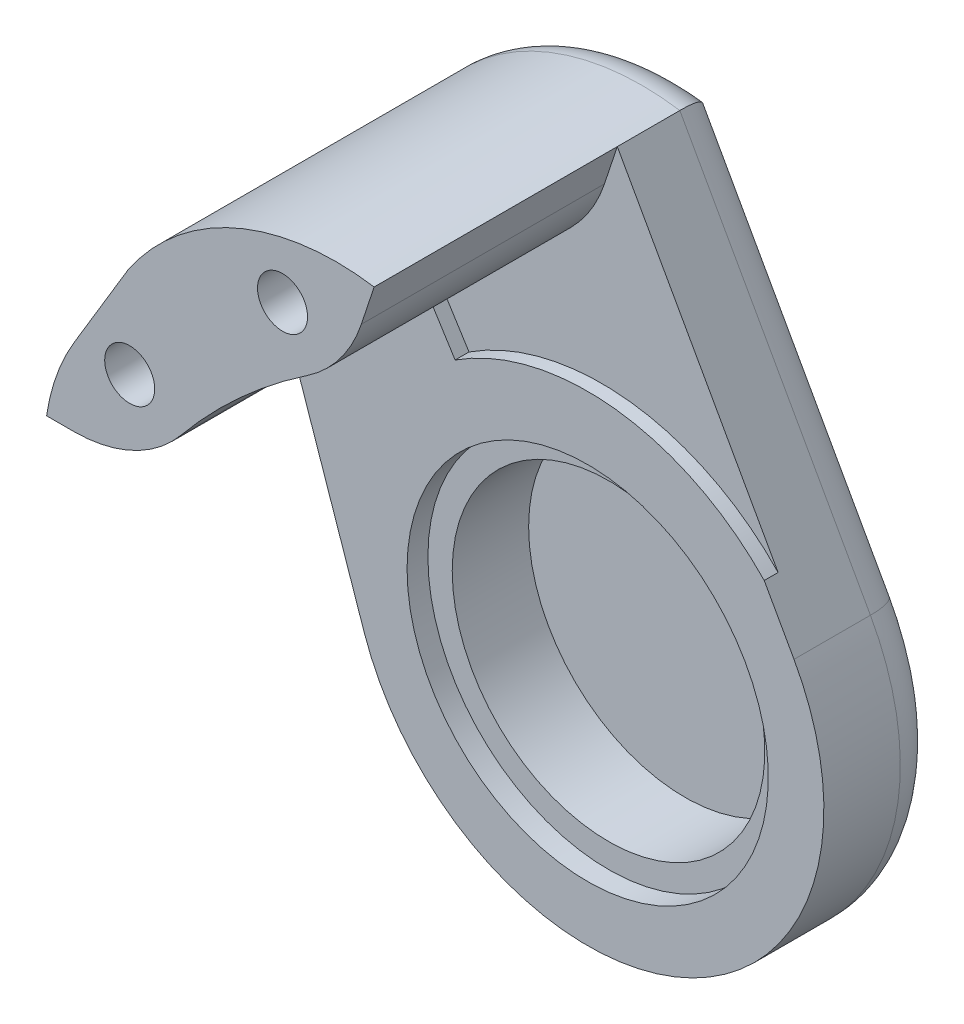
SolidWorks part; units mm, degrees
material "ABS"
ref_plane "Front Plane" through (0, 0, 0) normal (0, 0, 1) x (1, 0, 0)
ref_plane "Top Plane" through (0, 0, 0) normal (0, 1, 0) x (1, 0, 0)
ref_plane "Right Plane" through (0, 0, 0) normal (1, 0, 0) x (0, 0, -1)
sketch "Sketch1" plane through (0, 0, 0) normal (0, 0, 1) x (1, 0, 0)
  line L0 (-21.5118, -23.5649) -> (-14.5118, -23.5649)
  line L1 (0, -9.9671) -> (2.0631, -3.7458)
  line L3 (-15.6677, -11.5659) -> (-19.5301, -18.0027)
  arc A1 (-19.5301, -18.0027) -> (-21.5118, -23.5649) centre (-6.6677, -25.7195) ccw
  arc A2 (-15.6677, -11.5659) -> (2.0631, -3.7458) centre (-0.6677, -21.5651) cw
  arc A3 (-14.5118, -23.5649) -> (0, -9.9671) centre (21.0043, -46.9259) cw
  circle A4 centre (-4.5301, -8.0036) radius 1.8
  circle A5 centre (-15.5301, -18.0027) radius 1.8
  dimension "D1" = 7
  dimension "D8" = 3.6
  dimension "D2" = 2.0631
  dimension "D3" = 3.7458
  dimension "D4" = 16.9817
  dimension "D5" = 15.5614
  dimension "D6" = 5.9817
  dimension "D7" = 5.5622
extrude "Boss-Extrude1" add sketch "Sketch1" along normal blind 21
sketch "Sketch2" plane through (0, 0, 21) normal (0, 0, 1) x (1, 0, 0)
  line L0 (-15.6677, -11.5659) -> (-19.5301, -18.0027) construction
  line L1 (-15.6677, -11.5659) -> (-19.5301, -18.0027)
  line L2 (2.0631, -3.7458) -> (15.7796, -28.3476)
  line L3 (-21.5118, -23.5649) -> (-15.1513, -42.1348)
  arc A0 (-19.5301, -18.0027) -> (-21.5118, -23.5649) centre (-6.6677, -25.7195) ccw construction
  arc A1 (2.0631, -3.7458) -> (-15.6677, -11.5659) centre (-0.6677, -21.5651) ccw construction
  arc A2 (-19.5301, -18.0027) -> (-21.5118, -23.5649) centre (-6.6677, -25.7195) ccw
  arc A3 (2.0631, -3.7458) -> (-15.6677, -11.5659) centre (-0.6677, -21.5651) ccw
  arc A4 (15.7796, -28.3476) -> (-15.1513, -42.1348) centre (0.9315, -36.6261) cw
  circle A5 centre (-15.5301, -18.0027) radius 1.8 construction
  circle A6 centre (-4.5301, -8.0036) radius 1.8 construction
  circle A7 centre (-15.5301, -18.0027) radius 1.8
  circle A8 centre (-4.5301, -8.0036) radius 1.8
  dimension "D1" = 17
  dimension "D2" = 22.4433
  dimension "D3" = 13.0611
extrude "Boss-Extrude2" add sketch "Sketch2" along normal blind 4 and the other way blind 4.5
sketch "Sketch3" plane through (0, 0, 16.5) normal (0, 0, -1) x (-1, 0, 0)
  circle A0 centre (-0.9315, -36.6261) radius 11.25
  dimension "D1" = 22.5
  dimension "D2" = 32.8803
  dimension "D3" = 22.4433
extrude "Cut-Extrude1" cut sketch "Sketch3" against normal blind 7
sketch "Sketch4" plane through (0, 0, 16.5) normal (0, 0, -1) x (-1, 0, 0)
  circle A0 centre (-0.9315, -36.6261) radius 13
  dimension "D1" = 26
extrude "Cut-Extrude2" cut sketch "Sketch4" against normal blind 1.5
sketch "Sketch5" plane through (0, 0, 25) normal (0, 0, 1) x (1, 0, 0)
  circle A0 centre (-4.5301, -8.0036) radius 3
  circle A1 centre (-15.5301, -18.0027) radius 3
  dimension "D1" = 6
extrude "Cut-Extrude3" cut sketch "Sketch5" against normal blind 12
fillet "Fillet1" radius 3 6 edges at (-20.7974, -20.6853, 25) (8.9213, -16.0467, 25) (7.8526, -52.1534, 25) (-17.5989, -14.7843, 25) (-7.9425, -5.0708, 25) (-18.3315, -32.8499, 25)
sketch "Sketch6" plane through (0, 0, 16.5) normal (0, 0, -1) x (-1, 0, 0)
  line L0 (-2.0631, -3.7458) -> (0, -9.9671)
  line L1 (-2.0631, -3.7458) -> (-13.6368, -24.5042)
  line L2 (-15.7796, -28.3476) -> (-2.0631, -3.7458) construction
  line L3 (10.6831, -18.5879) -> (8.6095, -21.8839)
  arc A0 (-13.6368, -24.5042) -> (8.6095, -21.8839) centre (-0.9315, -36.6261) cw
  arc A1 (0, -9.9671) -> (10.6831, -18.5879) centre (-21.0043, -46.9259) cw
  arc A2 (14.5118, -23.5649) -> (0, -9.9671) centre (-21.0043, -46.9259) ccw construction
  dimension "D1" = 42.5104
  dimension "D2" = 17.5603
  dimension "D3" = 3.2959
  dimension "D4" = 10.6831
  dimension "D5" = 2.0736
  dimension "D6" = 11.5737
extrude "Cut-Extrude4" cut sketch "Sketch6" against normal blind 1
fillet "Fillet2" radius 10 2 edges at (-14.5118, -23.5649, 8.25) (0, -9.9671, 8.75)
ref_plane "Plane1" through (0, 0, -10) normal (0, 0, 1) x (1, 0, 0)
mirror "Mirror2" about plane through (0, 0, -10) normal (0, 0, 1) of bodies 106
sketch "Sketch8" plane through (-0.0194, -0.0108, 0) normal (0.8734, 0.487, 0) x (0, 0, -1)
  line L1 (-56.4869, 49.716) -> (3.681, 49.716)
  line L2 (-56.4869, 49.716) -> (-56.4869, -52.6244)
  line L3 (-56.4869, -52.6244) -> (3.681, -52.6244)
  line L4 (3.681, 49.716) -> (3.681, -52.6244)
  line L5 (-56.4869, 49.716) -> (3.681, -52.6244) construction
  line L6 (-56.4869, -52.6244) -> (3.681, 49.716) construction
  point P0 (-26.403, -1.4542)
extrude "Cut-Extrude5" cut sketch "Sketch8" against normal through all both and the other way through all
